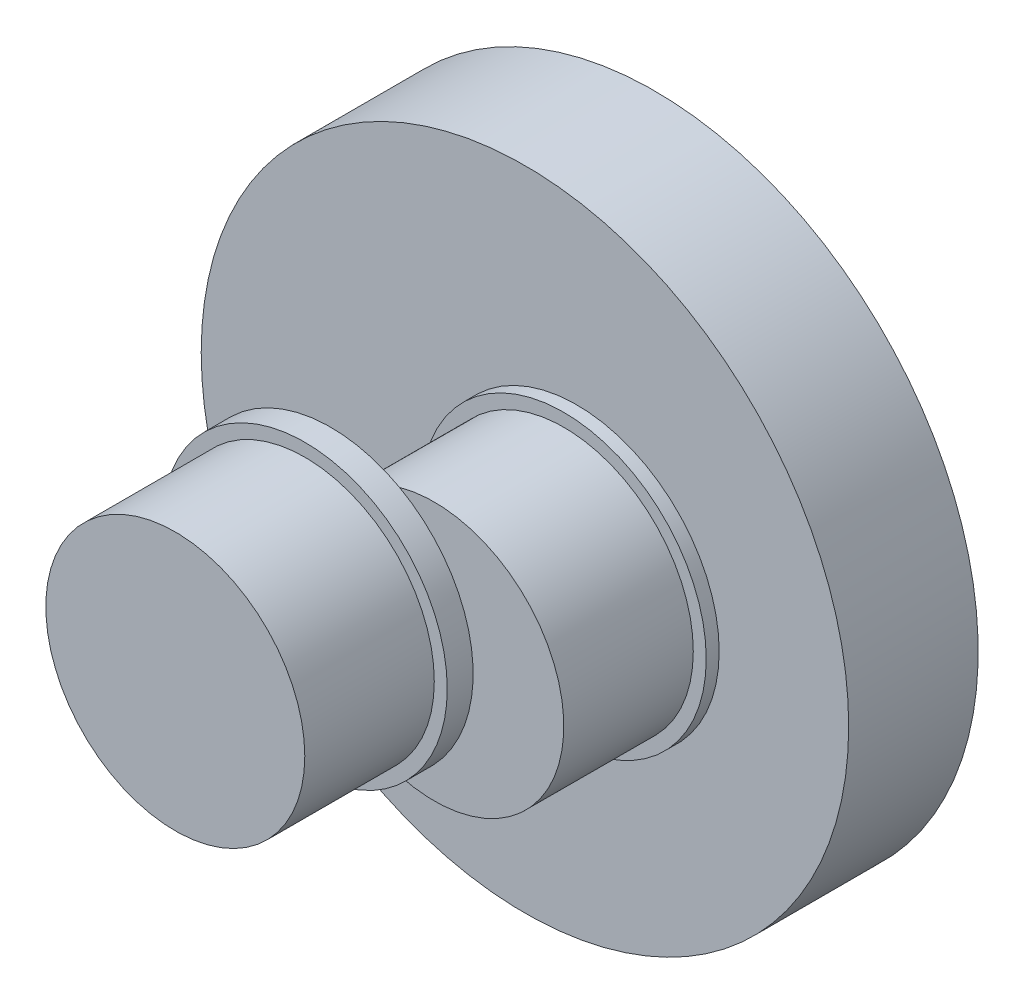
SolidWorks part; units mm, degrees
ref_plane "Front Plane" through (0, 0, 0) normal (0, 0, 1) x (1, 0, 0)
ref_plane "Top Plane" through (0, 0, 0) normal (0, 1, 0) x (1, 0, 0)
ref_plane "Right Plane" through (0, 0, 0) normal (1, 0, 0) x (0, 0, -1)
sketch "Sketch1" plane through (0, 0, -2) normal (0, 0, -1) x (-1, 0, 0)
  circle A0 centre (0, 0) radius 12.5
  dimension "D1" = 25
extrude "Boss-Extrude1" add sketch "Sketch1" against normal up to surface (5 mm away) contours A0
sketch "Sketch2" plane through (0, 0, 3) normal (0, 0, 1) x (1, 0, 0)
  line L0 (0, 0) -> (2, 0)
  circle A0 centre (2, 0) radius 5
  circle A1 centre (2, 0) radius 5.4995
  dimension "D2" = 10
extrude "Boss-Extrude2" add sketch "Sketch2" along normal blind 0.5 contours A1 A0 region at (-3.3439, 0, 3)
extrude "Boss-Extrude3" add sketch "Sketch2<3>" along normal blind 5.5 contours A0 region at (-2.8586, 0, 3)
sketch "Sketch2<3>" plane through (0, 0, 3) normal (0, 0, 1) x (1, 0, 0) same geometry as "Sketch2"
sketch "Sketch3" plane through (0, 0, 3) normal (0, 0, 1) x (1, 0, 0)
  line L0 (0, 0) -> (-2, 0)
  circle A0 centre (-2, 0) radius 5
  circle A1 centre (-2, 0) radius 5.5
  circle M1 centre (2, 0) radius 5.4995
  dimension "D2" = 10
  dimension "D3" = 11
extrude "Boss-Extrude4" add sketch "Sketch3" along normal blind 1 from surface contours A1 A0 M1 | A1 A0 M1 region at (2.0707, 3.0899, 3) region at (-7.1331, 0, 3) starting at face at (7, 0, 8.5)
extrude "Boss-Extrude5" add sketch "Sketch3<3>" along normal blind 6 from surface contours A0 M1 | A0 region at (1.8901, -2.9528, 3) region at (-4.3558, 0, 3) starting at face at (5.25, 0, 8.5)
sketch "Sketch3<3>" plane through (0, 0, 3) normal (0, 0, 1) x (1, 0, 0) same geometry as "Sketch3"
equation "\"CenterShaft\"=25"
equation "\"D1@Sketch1\"=\"CenterShaft\""
equation "\"Eccentricity\"=2"
equation "\"D1@Sketch2\"=\"Eccentricity\""
equation "\"CycCamShaft\"=10"
equation "\"D2@Sketch2\"=\"CycCamShaft\""
equation "\"D2@Sketch3\"=\"CycCamShaft\""
